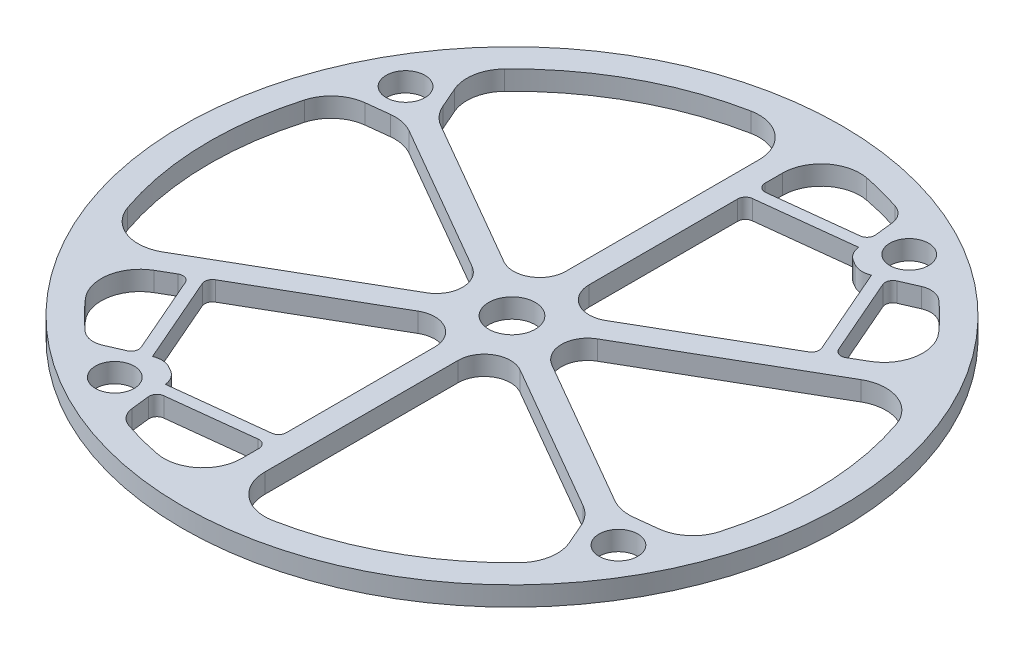
SolidWorks part; units mm, degrees
material "6063-T6"
ref_plane "Płaszczyzna przednia" through (0, 0, 0) normal (0, 0, 1) x (1, 0, 0)
ref_plane "Płaszczyzna górna" through (0, 0, 0) normal (0, 1, 0) x (1, 0, 0)
ref_plane "Płaszczyzna prawa" through (0, 0, 0) normal (1, 0, 0) x (0, 0, -1)
sketch "Szkic1" plane through (0, 0, 0) normal (0, 1, 0) x (1, 0, 0)
  circle A0 centre (0, 0) radius 85
  dimension "D1" = 170
extrude "Dodanie-wyciągnięcie1" add sketch "Szkic1" along normal blind 5
sketch "Szkic2" plane through (0, 5, 0) normal (0, 1, 0) x (1, 0, 0)
  line L0 (0, 0) -> (0, 85) construction
  line L1 (0, 85) -> (0, 75) construction
  line L2 (0, 64.5631) -> (3, 64.5631) construction
  line L3 (0, 64.5631) -> (-3, 64.5631) construction
  line L4 (3, 64.5631) -> (3, 9.5394)
  line L5 (-3, 64.5631) -> (-3, 9.5394)
  line L6 (-3, 64.5631) -> (-3, 77.9423) construction
  line L7 (3, 64.5631) -> (3, 77.9423) construction
  line L8 (3, 64.5631) -> (3, 77.9423)
  line L9 (-3, 77.9423) -> (-3, 64.5631)
  line L10 (57.4133, 29.6835) -> (69, 36.3731)
  line L11 (66, 41.5692) -> (54.4133, 34.8796)
  line L12 (54.4133, 34.8796) -> (6.7614, 7.3678)
  line L13 (57.4133, 29.6835) -> (9.7614, 2.1716)
  line L14 (-64.9519, 37.5) -> (0, 0) construction
  line L15 (-54.4133, 34.8796) -> (-59.2452, 45.9892)
  line L16 (57.4133, -29.6835) -> (9.7614, -2.1716)
  line L17 (54.4133, -34.8796) -> (6.7614, -7.3678)
  line L18 (-3, -64.5631) -> (-3, -77.9423)
  line L19 (3, -77.9423) -> (3, -64.5631)
  line L20 (3, -64.5631) -> (3, -9.5394)
  line L21 (-3, -64.5631) -> (-3, -9.5394)
  line L22 (-57.4133, -29.6835) -> (-69, -36.3731)
  line L23 (-66, -41.5692) -> (-54.4133, -34.8796)
  line L24 (-54.4133, -34.8796) -> (-6.7614, -7.3678)
  line L25 (-57.4133, -29.6835) -> (-9.7614, -2.1716)
  line L26 (-59.2452, 45.9892) -> (-60.6013, 49.1069)
  line L27 (-57.4133, 29.6835) -> (-69.4504, 28.3133)
  line L28 (-57.4133, 29.6835) -> (-9.7614, 2.1716)
  line L29 (-54.4133, 34.8796) -> (-6.7614, 7.3678)
  line L30 (39, 67.55) -> (0, 0) construction
  line L31 (39, 67.55) -> (42.5, 73.6122) construction
  line L32 (42.5, 73.6122) -> (37.5, 64.9519) construction
  line L33 (-54.4133, 34.8796) -> (-66, 41.5692) [skipped]
  line L34 (-69, 36.3731) -> (-57.4133, 29.6835) [skipped]
  line L35 (69, -36.3731) -> (57.4133, -29.6835) [skipped]
  line L36 (54.4133, -34.8796) -> (66, -41.5692) [skipped]
  line L37 (-69.4504, 28.3133) -> (-72.8284, 27.9288)
  line L38 (34.8796, 54.4133) -> (45.9892, 59.2452)
  line L39 (45.9892, 59.2452) -> (49.1069, 60.6013)
  line L40 (29.6835, 57.4133) -> (28.3133, 69.4504)
  line L41 (28.3133, 69.4504) -> (27.9288, 72.8284)
  line L42 (54.4133, -34.8796) -> (59.2452, -45.9892)
  line L43 (59.2452, -45.9892) -> (60.6013, -49.1069)
  line L44 (57.4133, -29.6835) -> (69.4504, -28.3133)
  line L45 (69.4504, -28.3133) -> (72.8284, -27.9288)
  line L46 (-34.8796, -54.4133) -> (-45.9892, -59.2452)
  line L47 (-45.9892, -59.2452) -> (-49.1069, -60.6013)
  line L48 (-29.6835, -57.4133) -> (-28.3133, -69.4504)
  line L49 (-28.3133, -69.4504) -> (-27.9288, -72.8284)
  circle A0 centre (0, 0) radius 85 construction
  circle A2 centre (0, 0) radius 10
  circle A3 centre (0, 0) radius 78 construction
  circle A4 centre (64.9519, -37.5) radius 5
  circle A5 centre (-37.5, -64.9519) radius 5
  circle A6 centre (-64.9519, 37.5) radius 5
  arc A7 (-57.4133, 29.6835) -> (-54.4133, 34.8796) centre (0, 0) cw
  circle A8 centre (0, 0) radius 75 construction
  arc A9 (-64.9519, 37.5) -> (-62.309, 41.7444) centre (0, 0) cw construction
  circle A10 centre (37.5, 64.9519) radius 5
  arc A11 (-62.309, 41.7444) -> (-59.2452, 45.9892) centre (0, 0) cw
  arc A12 (-64.9519, 37.5) -> (-67.3062, 33.0889) centre (0, 0) ccw construction
  arc A13 (-67.3062, 33.0889) -> (-69.4504, 28.3133) centre (0, 0) ccw
  circle A14 centre (0, 0) radius 64.6327 construction
  arc A15 (-60.6013, 49.1069) -> (-3, 77.9423) centre (0, 0) cw
  circle A16 centre (9.7614, 16.9072) radius 6.7614 construction
  arc A17 (3, 16.9072) -> (13.142, 11.0517) centre (9.7614, 16.9072) ccw
  arc A18 (49.1069, 60.6013) -> (77.9423, 3) centre (0, 0) cw
  arc A19 (29.6835, 57.4133) -> (34.8796, 54.4133) centre (0, 0) cw
  arc A20 (60.6013, -49.1069) -> (3, -77.9423) centre (0, 0) cw
  arc A21 (57.4133, -29.6835) -> (54.4133, -34.8796) centre (0, 0) cw
  arc A22 (-49.1069, -60.6013) -> (-77.9423, -3) centre (0, 0) cw
  arc A23 (-29.6835, -57.4133) -> (-34.8796, -54.4133) centre (0, 0) cw
  arc A24 (-77.9423, -3) -> (-72.8284, 27.9288) centre (0, 0) cw
  arc A25 (-27.9288, -72.8284) -> (-3, -77.9423) centre (0, 0) ccw
  arc A26 (72.8284, -27.9288) -> (77.9423, 3) centre (0, 0) ccw
  arc A27 (3, 77.9423) -> (27.9288, 72.8284) centre (0, 0) cw
  circle A28 centre (0, 0) radius 6
  arc A29 (16.142, 5.8555) -> (16.142, -5.8555) centre (19.5227, 0) ccw
  arc A30 (13.142, -11.0517) -> (3, -16.9072) centre (9.7614, -16.9072) ccw
  arc A31 (-3, -16.9072) -> (-13.142, -11.0517) centre (-9.7614, -16.9072) ccw
  arc A32 (-16.142, -5.8555) -> (-16.142, 5.8555) centre (-19.5227, 0) ccw
  arc A33 (-13.142, 11.0517) -> (-3, 16.9072) centre (-9.7614, 16.9072) ccw
  point P55 (0, 0)
  point P60 (0, 0)
  point P61 (0, 0)
  point P66 (0, 0)
  point P85 (0, 0)
  point P93 (0, 0)
  point P101 (0, 0)
  point P117 (0, 0)
  dimension "D1" = 6
  dimension "D2" = 20
  dimension "D3" = 4
  dimension "D4" = 4
  dimension "D5" = 6
extrude "Wytnij-wyciągnięcie2" cut sketch "Szkic2" against normal blind 5 contours A15 L26 L15 L29 A2 L5 L9 | A27 L8 L4 A2 L12 L11 A18 L39 L38 A19 L40 L41 | L45 A26 A18 L10 L13 A2 L16 L44 | A20 L43 L42 L17 A2 L20 L19 | L49 A25 L18 L21 A2 L24 L23 A22 L47 L46 A23 L48 | A24 A22 L22 L25 A2 L28 L27 L37 | A6 | A28 | A10 | A4 | A5 region at (25.4034, 5, -43.9999) region at (-25.4174, 5, -45.5103) region at (52.1217, 5, -0.7431) region at (-52.1217, 5, 0.7431) region at (-64.9519, 5, -37.5) region at (25.4174, 5, 45.5103) region at (-25.4034, 5, 43.9999) region at (37.5, 5, -64.9519) region at (0, 5, 0)
fillet "Zaokrąglenie2" radius 10 12 edges at (69, 2.5, -36.3731) (66, 2.5, -41.5692) (3, 2.5, -77.9423) (-3, 2.5, -77.9423) (3, 2.5, 77.9423) (-3, 2.5, 77.9423) (-66, 2.5, 41.5692) (-69, 2.5, 36.3731) (60.6013, 2.5, 49.1069) (72.8284, 2.5, 27.9288) (-60.6013, 2.5, -49.1069) (-72.8284, 2.5, -27.9288)
fillet "Zaokrąglenie4" radius 10 4 edges at (54.4133, 2.5, 34.8796) (57.4133, 2.5, 29.6835) (-57.4133, 2.5, -29.6835) (-54.4133, 2.5, -34.8796)
fillet "Zaokrąglenie5" radius 5 8 edges at (-27.9288, 2.5, 72.8284) (-29.6835, 2.5, 57.4133) (-34.8796, 2.5, 54.4133) (-49.1069, 2.5, 60.6013) (27.9288, 2.5, -72.8284) (29.6835, 2.5, -57.4133) (34.8796, 2.5, -54.4133) (49.1069, 2.5, -60.6013)
sketch "Szkic3" plane through (0, 5, 0) normal (0, 1, 0) x (1, 0, 0)
  line L0 (0, 0) -> (0, 89.563) construction
  line L1 (0, 0) -> (110.8114, 0) construction
  line L2 (3, 57) -> (29.3886, 60.0037)
  line L3 (3, 16.9072) -> (3, 66.7458) construction
  line L4 (29.3889, 60.0012) -> (28.28, 69.7431) construction
  line L5 (3, 60.0194) -> (29.0493, 62.9845)
  line L6 (29.0493, 62.9845) -> (29.3886, 60.0037)
  line L7 (3, 60.0194) -> (3, 57)
  line L8 (0, 0) -> (37.5, 64.9519) construction
  line L9 (40.0215, 56.6497) -> (37.2705, 55.4531)
  line L10 (50.4783, 32.6078) -> (47.8634, 31.0981)
  line L11 (50.4783, 32.6078) -> (40.0215, 56.6497)
  line L12 (47.8634, 31.0981) -> (37.2705, 55.4531)
  line L13 (0, 0) -> (-64.9519, 37.5) construction
  line L14 (-47.8634, -31.0981) -> (-37.2705, -55.4531)
  line L15 (-50.4783, -32.6078) -> (-47.8634, -31.0981)
  line L16 (-40.0215, -56.6497) -> (-37.2705, -55.4531)
  line L17 (-50.4783, -32.6078) -> (-40.0215, -56.6497)
  line L18 (-3, -60.0194) -> (-3, -57)
  line L19 (-29.0493, -62.9845) -> (-29.3886, -60.0037)
  line L20 (-3, -57) -> (-29.3886, -60.0037)
  line L21 (-3, -60.0194) -> (-29.0493, -62.9845)
  dimension "D1" = 57
  dimension "D2" = 3
extrude "Dodanie-wyciągnięcie2" add sketch "Szkic3" against normal through all
fillet "Zaokrąglenie6" radius 2 12 edges at (-3, 2.5, 57) (-40.0215, 2.5, 56.6497) (-47.8634, 2.5, 31.0981) (-50.4783, 2.5, 32.6078) (-3, 2.5, 60.0194) (-29.0493, 2.5, 62.9845) (50.4783, 2.5, -32.6078) (47.8634, 2.5, -31.0981) (40.0215, 2.5, -56.6497) (3, 2.5, -57) (29.0493, 2.5, -62.9845) (3, 2.5, -60.0194)
